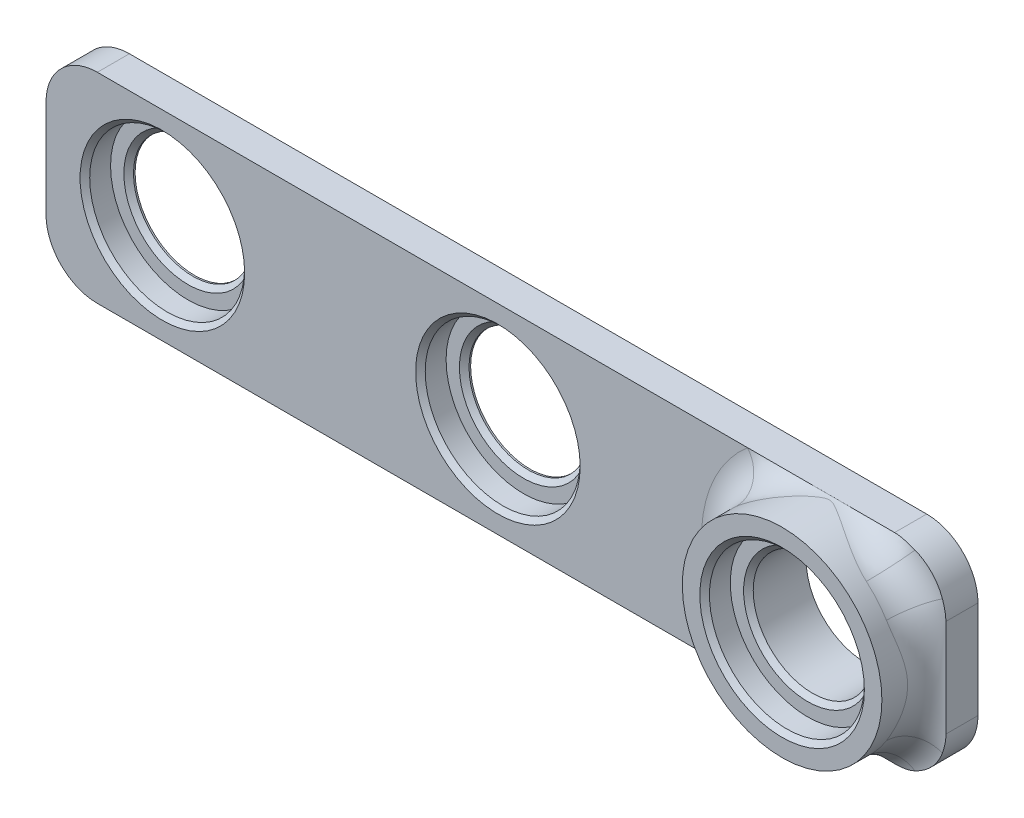
SolidWorks part; units mm, degrees
ref_plane "Alzado" through (0, 0, 0) normal (0, 0, 1) x (1, 0, 0)
ref_plane "Planta" through (0, 0, 0) normal (0, 1, 0) x (1, 0, 0)
ref_plane "Vista lateral" through (0, 0, 0) normal (1, 0, 0) x (0, 0, -1)
sketch "Croquis1" plane through (0, 0, 0) normal (0, 0, 1) x (1, 0, 0)
  line L0 (0, 23.9911) -> (0, -22.7284) construction
  line L1 (-44.2877, 15.5988) -> (44.2877, 15.5988)
  line L2 (-44.2877, 15.5988) -> (-44.2877, -15.5988)
  line L3 (-44.2877, -15.5988) -> (44.2877, -15.5988)
  line L4 (44.2877, 15.5988) -> (44.2877, -15.5988)
  line L5 (-44.2877, 15.5988) -> (44.2877, -15.5988) construction
  line L6 (-44.2877, -15.5988) -> (44.2877, 15.5988) construction
  circle A0 centre (-26.15, 0) radius 12.075
  circle A1 centre (26.15, 0) radius 12.075
  point P0 (0, 0)
  dimension "D1" = 24.15
  dimension "D2" = 52.3
extrude "Saliente-Extruir1" add sketch "Croquis1" along normal blind 5
sketch "Croquis2" plane through (0, 0, 0) normal (0, 0, -1) x (-1, 0, 0)
  line L1 (44.2877, -15.5988) -> (-44.2877, -15.5988)
  line L2 (44.2877, -15.5988) -> (44.2877, 15.5988)
  line L3 (44.2877, 15.5988) -> (-44.2877, 15.5988)
  line L4 (-44.2877, -15.5988) -> (-44.2877, 15.5988)
  line L5 (44.2877, -15.5988) -> (-44.2877, 15.5988) construction
  line L6 (44.2877, 15.5988) -> (-44.2877, -15.5988) construction
  circle A0 centre (-26.15, 0) radius 9.25
  circle A1 centre (26.15, 0) radius 9.25
  point P0 (0, 0)
  dimension "D1" = 18.5
extrude "Saliente-Extruir2" add sketch "Croquis2" against normal blind 1
sketch "Croquis3" plane through (0, 0, 0) normal (0, 0, -1) x (-1, 0, 0)
  line L0 (44.2877, -15.5988) -> (-44.2877, -15.5988) construction
  line L1 (-44.2877, 15.5988) -> (-95.9856, 15.5988)
  line L2 (-44.2877, 15.5988) -> (-44.2877, -15.5988)
  line L3 (-44.2877, -15.5988) -> (-95.9856, -15.5988)
  line L4 (-95.9856, 15.5988) -> (-95.9856, -15.5988)
  line L5 (-26.15, 0) -> (-26.15, 7.1702) construction
  circle A0 centre (-78.45, 0) radius 9.25
  circle A1 centre (-26.15, 0) radius 9.25 construction
  dimension "D1" = 52.3
extrude "Saliente-Extruir3" add sketch "Croquis3" against normal up to surface (5 mm away) up to face at (-14.075, 0, 5)
sketch "Croquis4" plane through (0, 0, 5) normal (0, 0, 1) x (1, 0, 0)
  circle A0 centre (78.45, 0) radius 15.5585
  circle A1 centre (78.45, 0) radius 9.25
extrude "Saliente-Extruir4" add sketch "Croquis4" along normal blind 8
sketch "Croquis5" plane through (0, 0, 13) normal (0, 0, 1) x (1, 0, 0)
  circle A0 centre (78.45, 0) radius 12.075
  circle A1 centre (26.15, 0) radius 12.075 construction
extrude "Cortar-Extruir1" cut sketch "Croquis5" against normal blind 4
chamfer "Chaflán1" distance 0.75 angle 45 3 edges at (-14.075, 0, 5) (38.225, 0, 5) (90.525, 0, 13)
fillet "Redondeo2" radius 5 1 edges at (94.0085, 0, 5)
fillet "Redondeo1" radius 8 4 edges at (-44.2877, -15.5988, 2.5) (-44.2877, 15.5988, 2.5) (95.9856, 15.5988, 2.5) (95.9856, -15.5988, 2.5)
chamfer "Chaflán2" distance 0.75 angle 45 3 edges at (87.7, 0, 9) (16.9, 0, 1) (-35.4, 0, 1)
